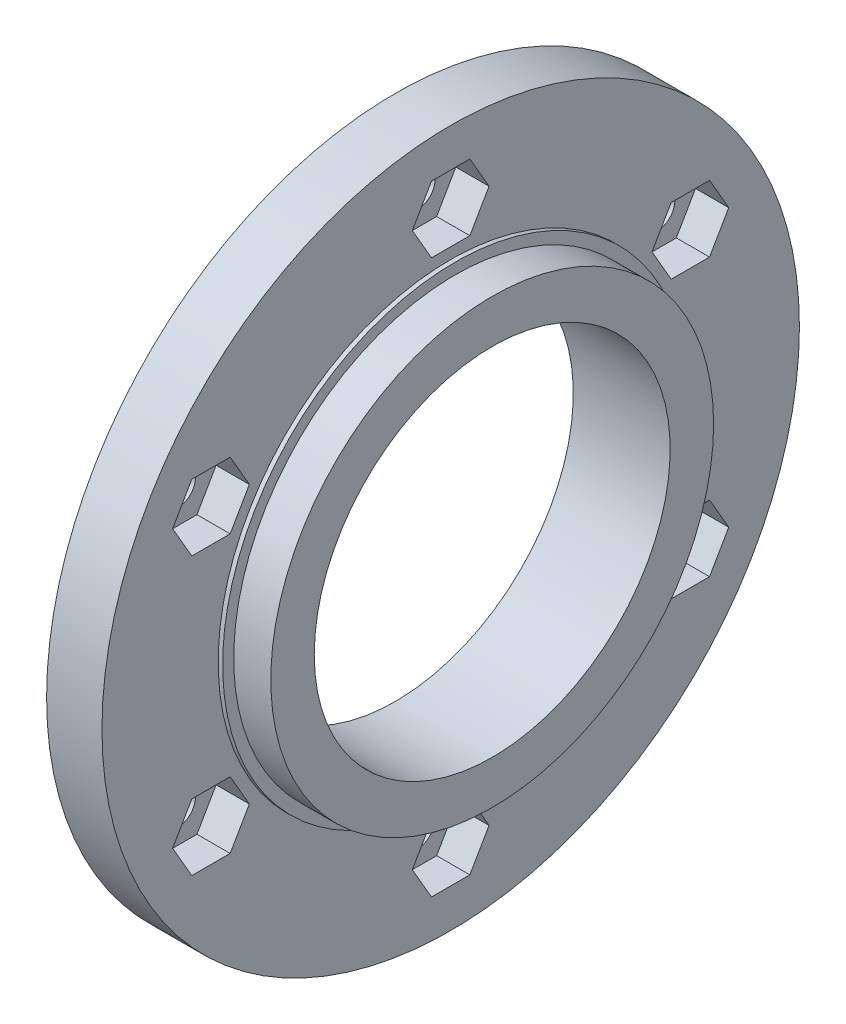
SolidWorks part; units mm, degrees
ref_plane "Ebene vorne" through (0, 0, 0) normal (0, 0, 1) x (1, 0, 0)
ref_plane "Ebene oben" through (0, 0, 0) normal (0, 1, 0) x (1, 0, 0)
ref_plane "Ebene rechts" through (0, 0, 0) normal (1, 0, 0) x (0, 0, -1)
sketch "Skizze1" plane through (0, 0, 0) normal (0, 0, 1) x (1, 0, 0)
  line L0 (0, 0) -> (-40471.317, 0) construction
  line L1 (0, 0) -> (0, 31.5)
  line L2 (0, 31.5) -> (5, 31.5)
  line L3 (5, 31.5) -> (5, 21)
  line L4 (5, 21) -> (5.4, 21)
  line L6 (8.75, 0) -> (0, 0)
  line L7 (8.75, 0) -> (8.75, 20)
  line L8 (8.75, 20) -> (5.4, 20)
  line L9 (5.4, 21) -> (5.4, 20)
  dimension "D1" = 42
  dimension "D2" = 0.4
  dimension "D3" = 3.35
  dimension "D4" = 63
  dimension "D5" = 40
  dimension "D6" = 8.75
revolve "Rotation1" add sketch "Skizze1" angle 360 about L0
sketch "Skizze2" plane through (0, 0, 0) normal (-1, 0, 0) x (0, 0, 1)
  circle A0 centre (0, 0) radius 16.075
  dimension "D1" = 32.15
extrude "Schnitt-Linear austragen1" cut sketch "Skizze2" against normal through all
sketch "Skizze3" plane through (5, 0, 0) normal (1, 0, 0) x (0, 0, -1)
  line L0 (0, 0) -> (0, -50000) construction
  line L2 (1.7321, 22) -> (3.4641, 25)
  line L3 (3.4641, 25) -> (1.7321, 28)
  line L4 (1.7321, 28) -> (-1.7321, 28)
  line L5 (-1.7321, 28) -> (-3.4641, 25)
  line L6 (-3.4641, 25) -> (-1.7321, 22)
  line L7 (-1.7321, 22) -> (1.7321, 22)
  circle A0 centre (0, 25) radius 3 construction
  circle A1 centre (0, 0) radius 25 construction
  dimension "D2" = 50
  dimension "D1" = 6
extrude "Schnitt-Linear austragen2" cut sketch "Skizze3" against normal blind 3
pattern_circular "Kreismuster1" count 6 over 360 about axis through (8.75, 0, 0) along (-1, 0, 0) of "Schnitt-Linear austragen2"
hole_wizard "Ø3.2 (3.2) Durchmesser Bohrung1" positions "Skizze4" profile "Skizze5" hole size "Ø3.2" standard "ISO" end condition through all
sketch "Skizze4" plane through (5, 0, 0) normal (1, 0, 0) x (0, 0, -1)
  line L0 (0, 0) -> (0, -50000) construction
  circle A0 centre (0, 0) radius 25 construction
  point P9 (0, 25)
  dimension "D1" = 50
sketch "Skizze5" plane through (5, 25, 0) normal (0, 1, 0) x (0, 0, -1)
  line L0 (0, 0) -> (0, 5)
  line L1 (0, 5) -> (1.6, 5)
  line L2 (1.6, 5) -> (1.6, 0)
  line L5 (1.6, 0) -> (0, 0)
  line L11 (0, -6.35) -> (0, 107.95) construction
  dimension "Bohrerdurchmesser" = 3.2
  dimension "Bohrungstiefe" = 5
pattern_circular "Kreismuster2" count 6 over 360 about axis through (8.75, 0, 0) along (-1, 0, 0) of "Ø3.2 (3.2) Durchmesser Bohrung1"
